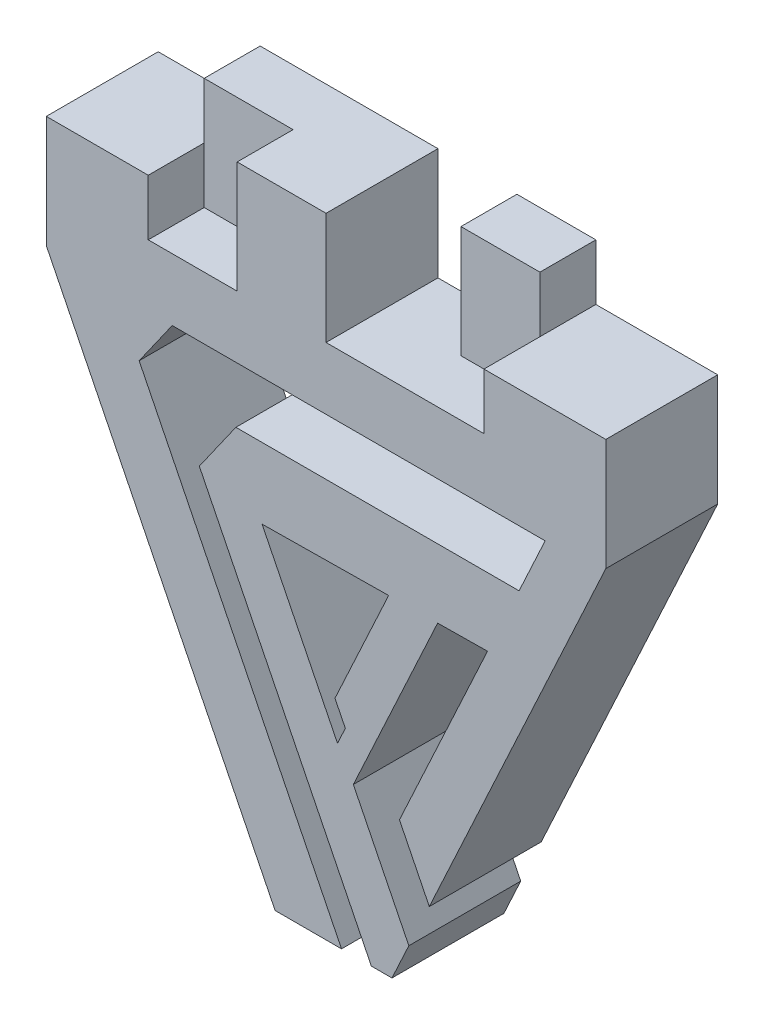
SolidWorks part; units mm, degrees
note: The reader was unsure of these and kept them because the rebuilt part matched: shared geometry of "草图3<6>".
ref_plane "前视基准面" through (0, 0, 0) normal (0, 0, 1) x (1, 0, 0)
ref_plane "上视基准面" through (0, 0, 0) normal (0, 1, 0) x (1, 0, 0)
ref_plane "右视基准面" through (0, 0, 0) normal (1, 0, 0) x (0, 0, -1)
sketch "草图2" plane through (0, 0, 0) normal (0, 0, 1) x (1, 0, 0)
  line L0 (-397.0128, -290.7794) -> (-396.3141, -290.7794)
  line L1 (-492.8377, -36.6006) -> (-292.8377, -36.6006)
  line L2 (-411.0435, -201.5478) -> (-492.8377, -36.6006)
  line L3 (-355.9291, -172.7522) -> (-292.8377, -36.6006)
  line L4 (-415.711, -84.2679) -> (-370.4625, -83.7308)
  line L5 (-370.4625, -83.7308) -> (-389.6473, -125.1317)
  line L6 (-389.6473, -125.1317) -> (-385.9436, -132.6007)
  line L7 (-376.0923, -105.2989) -> (-376.2501, -105.2989)
  line L8 (-415.711, -84.2679) -> (-388.7454, -138.647)
  line L9 (-411.0435, -201.5478) -> (-387.3021, -201.5478)
  line L10 (-447.3432, -58.9737) -> (-323.8435, -58.9737)
  line L11 (-447.3432, -58.9737) -> (-376.6435, -201.5478)
  line L12 (-385.9436, -132.6007) -> (-388.7454, -138.647)
  line L13 (-387.3021, -201.5478) -> (-459.6489, -55.6524)
  line L14 (-314.5162, -38.8453) -> (-447.8244, -38.8453)
  line L15 (-363.2483, -188.5469) -> (-383.0803, -148.5533)
  line L16 (-383.0803, -148.5533) -> (-352.9458, -83.5229)
  line L17 (-352.9458, -83.5229) -> (-335.1213, -83.3113)
  line L18 (-335.1213, -83.3113) -> (-366.5978, -151.2376)
  line L19 (-366.5978, -151.2376) -> (-355.9291, -172.7522)
  line L20 (-369.2728, -201.5478) -> (-363.2483, -188.5469)
  line L21 (-376.6435, -201.5478) -> (-369.2728, -201.5478)
  line L22 (-323.8435, -58.9737) -> (-314.5162, -38.8453)
  line L23 (-492.8377, -36.6006) -> (-492.8377, 3.3994)
  line L24 (-492.8377, 3.3994) -> (-292.8377, 3.3994)
  line L25 (-292.8377, 3.3994) -> (-292.8377, -36.6006)
  line L26 (-447.8244, -38.8453) -> (-459.6489, -55.6524)
  line L27 (-425.0686, -58.9737) -> (-438.1342, -77.5448)
extrude "凸台-拉伸1" add sketch "草图2" along normal blind 40
sketch "草图3" plane through (0, 3.3994, 0) normal (0, 1, 0) x (1, 0, 0)
  line L0 (-292.8377, 0) -> (-336.3918, 0)
  line L5 (-292.8377, -40) -> (-292.8377, 0) construction
  line L10 (-492.8377, 0) -> (-456.3918, 0)
  line L15 (-492.8377, 0) -> (-292.8377, 0)
  line L16 (-492.8377, 0) -> (-492.8377, -40)
  line L17 (-492.8377, -40) -> (-292.8377, -40)
  line L19 (-292.8377, 0) -> (-292.8377, -40)
  line L20 (-492.8377, 0) -> (-456.3918, 0)
  line L21 (-492.8377, 0) -> (-492.8377, -40)
  line L22 (-492.8377, -40) -> (-456.3918, -40)
  line L23 (-456.3918, 0) -> (-456.3918, -40)
  line L24 (-292.8377, 0) -> (-336.3918, 0)
  line L26 (-292.8377, 0) -> (-292.8377, -40)
  line L27 (-292.8377, -40) -> (-336.3918, -40)
  line L28 (-336.3918, 0) -> (-336.3918, -40)
  line L29 (-336.3918, 0) -> (-292.8377, 0)
  line L30 (-492.8377, -20) -> (-292.8377, -20)
  line L31 (-392.8377, -20) -> (-392.8377, 0)
  line L32 (-392.8377, -20) -> (-392.8377, -40)
  line L33 (-392.8377, -20) -> (-456.3918, -20)
  line L34 (-456.3918, -20) -> (-424.6147, -20)
  line L35 (-424.6147, -20) -> (-424.6147, -40)
  line L36 (-392.8377, -20) -> (-336.3918, -20)
  line L37 (-336.3918, -20) -> (-364.6147, -20)
  line L38 (-364.6147, -20) -> (-364.6147, 0)
extrude "凸台-拉伸5" add sketch "草图3" along normal blind 20
extrude "切除-拉伸1" cut sketch "草图3<6>" against normal blind 20
sketch "草图3<6>" plane through (0, 3.3994, 0) normal (0, 1, 0) x (1, 0, 0) same geometry as "草图3"
shell "抽壳1" thickness 4 removed face at (-385.073, -70.0771, 0)
